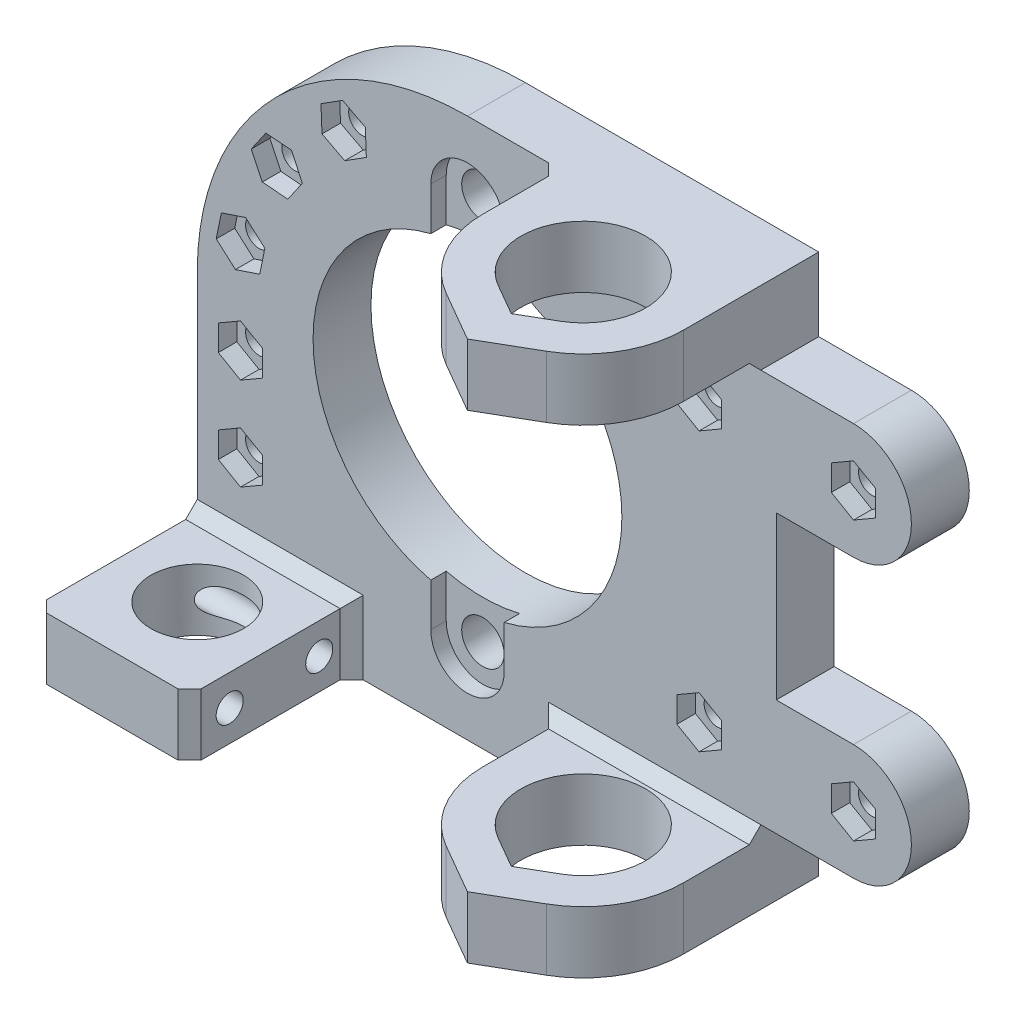
SolidWorks part; units mm, degrees
ref_plane "Front Plane" through (0, 0, 0) normal (0, 0, 1) x (1, 0, 0)
ref_plane "Top Plane" through (0, 0, 0) normal (0, 1, 0) x (1, 0, 0)
ref_plane "Right Plane" through (0, 0, 0) normal (1, 0, 0) x (0, 0, -1)
sketch "Sketch1" plane through (0, 0, 0) normal (0, 1, 0) x (1, 0, 0)
  line L0 (-62.4163, 0) -> (61.9965, 0) construction
  line L1 (-36.5, 35) -> (36.5, 35)
  line L2 (-36.5, 35) -> (-36.5, -35)
  line L3 (-36.5, -35) -> (36.5, -35)
  line L4 (36.5, 35) -> (36.5, -35) construction
  line L5 (-36.5, 35) -> (36.5, -35) construction
  line L6 (-36.5, -35) -> (36.5, 35) construction
  line L7 (36.5, 35) -> (36.5, 25.5)
  line L8 (36.5, 25.5) -> (48.5, 25.5)
  line L9 (48.5, 10.5) -> (38.5, 10.5)
  line L10 (38.5, 10.5) -> (38.5, -10.5)
  line L11 (48.5, -10.5) -> (38.5, -10.5)
  line L12 (36.5, -25.5) -> (48.5, -25.5)
  line L13 (36.5, -35) -> (36.5, -25.5)
  arc A0 (48.5, 25.5) -> (48.5, 10.5) centre (48.5, 18) cw
  arc A1 (48.5, -25.5) -> (48.5, -10.5) centre (48.5, -18) ccw
  point P0 (0, 0)
  point P15 (38.5, 0)
  dimension "D1" = 73
  dimension "D2" = 70
  dimension "D3" = 75
  dimension "D4" = 15
  dimension "D5" = 10
  dimension "D6" = 9.5
extrude "Boss-Extrude1" add sketch "Sketch1" along normal blind 7.5
sketch "Sketch3" plane through (0, 0, 35) normal (0, 0, 1) x (1, 0, 0)
  line L0 (36.5, 7.5) -> (36.5, 0) construction
  line L1 (36.5, 7.5) -> (10.5, 7.5)
  line L2 (36.5, 7.5) -> (36.5, 17.5)
  line L3 (36.5, 17.5) -> (10.5, 17.5) construction
  line L4 (10.5, 7.5) -> (10.5, 17.5)
  line L5 (-36.5, 7.5) -> (36.5, 7.5) construction
  line L6 (-36.5, 0) -> (36.5, 0) construction
  line L7 (23.5, 17.5) -> (23.5, 40.9913) construction
  line L8 (17, 28.7583) -> (23.5, 32.5111)
  line L9 (19.4625, 24.4932) -> (23.5, 26.8242)
  line L10 (17, 28.7583) -> (23.5, 17.5) construction
  line L11 (27.5375, 24.4932) -> (23.5, 26.8242)
  line L12 (30, 28.7583) -> (23.5, 32.5111)
  arc A0 (19.4625, 24.4932) -> (27.5375, 24.4932) centre (23.5, 17.5) ccw
  arc A1 (10.5, 17.5) -> (17, 28.7583) centre (23.5, 17.5) cw
  arc A2 (30, 28.7583) -> (36.5, 17.5) centre (23.5, 17.5) cw
  point P10 (23.5, 17.5)
  dimension "D3" = 16.15
  dimension "D1" = 26
  dimension "D2" = 17.5
  dimension "D4" = 120
extrude "Boss-Extrude3" add sketch "Sketch3" against normal blind 8
mirror "Mirror1" about plane through (0, 0, 0) normal (0, 0, 1) of "Boss-Extrude3"
sketch "Sketch10" plane through (0, 0, 0) normal (0, -1, 0) x (1, 0, 0)
  line L1 (-36.5, 27) -> (-16.5, 27)
  line L2 (-36.5, 27) -> (-36.5, 35)
  line L3 (-36.5, 35) -> (-16.5, 35)
  line L4 (-16.5, 27) -> (-16.5, 35)
  line L6 (-36.5, 35) -> (36.5, 35) construction
  line L7 (31.575, 35) -> (15.425, 35) construction
  point P9 (23.5, 35)
  point P14 (-26.5, 35)
  dimension "D1" = 8
  dimension "D4" = 50
extrude "Boss-Extrude4" add sketch "Sketch10" against normal offset from surface (28.5 mm away) 21 up to face at (22.7812, 7.5, -0.2031) offset beyond the face yes
sketch "Sketch11" plane through (0, 0, 35) normal (0, 0, 1) x (1, 0, 0)
  circle A0 centre (-26.5, 17.5) radius 6
  point P2 (23.5, 17.5)
  dimension "D1" = 12
  dimension "D2" = 50
extrude "Cut-Extrude6" cut sketch "Sketch11" against normal up to next
sketch "Sketch12" plane through (-36.5, 0, 0) normal (-1, 0, 0) x (0, 0, 1)
  line L0 (27, 17.5) -> (35, 17.5) construction
  line L1 (27, 28.5) -> (27, 7.5) construction
  line L2 (35, 28.5) -> (35, 0) construction
  line L3 (27, 23.5) -> (27, 11.5) construction
  circle A0 centre (31, 23.3) radius 1.75
  circle A1 centre (31, 11.7) radius 1.75
  point P12 (31, 21.55)
  point P13 (31, 13.45)
  point P14 (31, 17.5)
  dimension "D2" = 3.5
  dimension "D1" = 8.1
extrude "Cut-Extrude7" cut sketch "Sketch12" against normal up to next
sketch "Sketch6" plane through (0, 0, 0) normal (0, -1, 0) x (1, 0, 0)
  line L0 (-36.5, -35) -> (-36.5, 35) construction
  line L3 (-36.5, 35) -> (36.5, 35) construction
  line L5 (-20.5, 35) -> (-32.5, 35) construction
  line L6 (31.575, 35) -> (15.425, 35) construction
  line L7 (-26.5, 35) -> (23.5, 35) construction
  line L9 (-1.5, 35) -> (-1.5, 0) construction
  circle A0 centre (-1.5, 0) radius 20
  point P3 (-26.5, 35)
  point P5 (-36.5, 0)
  point P10 (23.5, 35)
  point P18 (-1.5, 35)
  dimension "D1" = 40
extrude "Cut-Extrude3" cut sketch "Sketch6" against normal through all
sketch "Sketch15" plane through (0, 0, 0) normal (0, -1, 0) x (1, 0, 0)
  line L0 (-1.5, 35) -> (-1.5, -35) construction
  line L1 (-36.5, 35) -> (36.5, 35) construction
  line L2 (36.5, -35) -> (-36.5, -35) construction
  line L3 (-21.5, 0) -> (18.5, 0) construction
  circle A1 centre (-1.5, 0) radius 20 construction
  circle A2 centre (-1.5, 25) radius 2.75
  circle A3 centre (-1.5, -25) radius 2.75
  point P8 (-1.5, 0)
  dimension "D1" = 5.5
  dimension "D2" = 25
extrude "Cut-Extrude9" cut sketch "Sketch15" against normal through all
sketch "Sketch14" plane through (0, 0, 0) normal (0, -1, 0) x (1, 0, 0)
  line L0 (0, 0) -> (89.7656, 0) construction
  line L1 (38.5, -10.5) -> (38.5, -25.5333) construction
  circle A0 centre (48.5, -18) radius 1.75
  circle A1 centre (28.5, -18) radius 1.75
  circle A2 centre (48.5, 18) radius 1.75
  circle A3 centre (28.5, 18) radius 1.75
  dimension "D1" = 3.5
  dimension "D2" = 20
extrude "Cut-Extrude8" cut sketch "Sketch14" against normal through all
sketch "Sketch19" plane through (0, 7.5, 0) normal (0, 1, 0) x (1, 0, 0)
  line L0 (38.5, 0) -> (82.8981, 0) construction
  line L1 (38.5, -10.5) -> (38.5, 10.5) construction
  line L2 (28.5, -18) -> (48.5, -18) construction
  line L3 (38.5, -18) -> (38.5, 0) construction
  line L4 (25.625, -16.3401) -> (28.5, -14.6802)
  line L5 (48.5, -14.6802) -> (45.625, -16.3401)
  line L6 (45.625, -16.3401) -> (45.625, -19.6599)
  line L7 (45.625, -19.6599) -> (48.5, -21.3198)
  line L8 (48.5, -21.3198) -> (51.375, -19.6599)
  line L9 (51.375, -19.6599) -> (51.375, -16.3401)
  line L10 (51.375, -16.3401) -> (48.5, -14.6802)
  line L11 (25.625, -19.6599) -> (25.625, -16.3401)
  line L12 (28.5, -21.3198) -> (25.625, -19.6599)
  line L13 (31.375, -19.6599) -> (28.5, -21.3198)
  line L14 (31.375, -16.3401) -> (31.375, -19.6599)
  line L15 (28.5, -14.6802) -> (31.375, -16.3401)
  line L16 (48.5, 21.3198) -> (51.375, 19.6599)
  line L17 (45.625, 19.6599) -> (48.5, 21.3198)
  line L18 (51.375, 16.3401) -> (48.5, 14.6802)
  line L19 (51.375, 19.6599) -> (51.375, 16.3401)
  line L20 (45.625, 16.3401) -> (45.625, 19.6599)
  line L21 (48.5, 14.6802) -> (45.625, 16.3401)
  line L22 (28.5, 14.6802) -> (31.375, 16.3401)
  line L23 (31.375, 16.3401) -> (31.375, 19.6599)
  line L24 (31.375, 19.6599) -> (28.5, 21.3198)
  line L25 (28.5, 21.3198) -> (25.625, 19.6599)
  line L26 (25.625, 19.6599) -> (25.625, 16.3401)
  line L27 (25.625, 16.3401) -> (28.5, 14.6802)
  circle A0 centre (48.5, -18) radius 2.875 construction
  circle A1 centre (48.5, 18) radius 2.875 construction
  dimension "D1" = 5.75
extrude "Cut-Extrude13" cut sketch "Sketch19" against normal blind 2.4
fillet "Fillet2" radius 35 1 edges at (-36.5, 3.75, -35)
chamfer "Chamfer2" distance 1.5 angle 45 8 edges at (-16.5, 28.5, 31) (-36.5, 28.5, 31) (-26.5, 7.5, 27) (-16.5, 7.5, 31) (23.5, 7.5, -27) (10.5, 7.5, -31)
sketch "Sketch17" plane through (0, 0, 0) normal (0, -1, 0) x (1, 0, 0)
  line L0 (-1.5, 0) -> (-36.5, 0) construction
  line L1 (-1.5, 0) -> (-16.5, -25.9808) construction
  line L2 (-1.5, 0) -> (-27.4808, 15) construction
  line L3 (-26.1909, 17.04) -> (-30.8939, 6) construction
  line L4 (-30.8939, 6) -> (-30.8939, -6) construction
  line L5 (-30.8939, -6) -> (-26.1909, -17.04) construction
  line L6 (-26.1909, -17.04) -> (-17.5373, -25.3536) construction
  line L7 (-30.8939, 6) -> (-30.8939, 18) construction
  circle A0 centre (-1.5, 0) radius 30 construction
  circle A1 centre (-30.8939, 6) radius 1.75
  circle A2 centre (-30.8939, -6) radius 1.75
  circle A3 centre (-30.8939, 18) radius 1.75
  circle A4 centre (-26.1909, -17.04) radius 1.75
  circle A5 centre (-17.5373, -25.3536) radius 1.75
  point P0 (-1.5, 0)
  point P5 (-31.5, 0)
  dimension "D2" = 60
  dimension "D5" = 3.5
  dimension "D1" = 30
  dimension "D3" = 5
  dimension "D4" = 12
extrude "Cut-Extrude11" cut sketch "Sketch17" against normal up to next
sketch "Sketch18" plane through (0, 7.5, 0) normal (0, 1, 0) x (1, 0, 0)
  line L0 (-30.8939, -18) -> (-1.5, 0) construction
  line L1 (-28.0189, -19.6599) -> (-28.0189, -16.3401)
  line L2 (-28.0189, -16.3401) -> (-30.8939, -14.6802)
  line L3 (-30.8939, -14.6802) -> (-33.7689, -16.3401)
  line L4 (-33.7689, -16.3401) -> (-33.7689, -19.6599)
  line L5 (-33.7689, -19.6599) -> (-30.8939, -21.3198)
  line L6 (-30.8939, -21.3198) -> (-28.0189, -19.6599)
  line L7 (-28.0189, -4.3401) -> (-30.8939, -2.6802)
  line L8 (-30.8939, -2.6802) -> (-33.7689, -4.3401)
  line L9 (-33.7689, -4.3401) -> (-33.7689, -7.6599)
  line L10 (-33.7689, -7.6599) -> (-30.8939, -9.3198)
  line L11 (-30.8939, -9.3198) -> (-28.0189, -7.6599)
  line L12 (-28.0189, -7.6599) -> (-28.0189, -4.3401)
  line L13 (-27.745, 7.0513) -> (-30.2299, 9.2527)
  line L14 (-30.2299, 9.2527) -> (-33.3788, 8.2013)
  line L15 (-33.3788, 8.2013) -> (-34.0428, 4.9487)
  line L16 (-34.0428, 4.9487) -> (-31.5578, 2.7473)
  line L17 (-31.5578, 2.7473) -> (-28.4089, 3.7987)
  line L18 (-28.4089, 3.7987) -> (-27.745, 7.0513)
  line L19 (-22.8818, 16.7731) -> (-24.3052, 19.7723)
  line L20 (-24.3052, 19.7723) -> (-27.6143, 20.0391)
  line L21 (-27.6143, 20.0391) -> (-29.4999, 17.3069)
  line L22 (-29.4999, 17.3069) -> (-28.0765, 14.3077)
  line L23 (-28.0765, 14.3077) -> (-24.7675, 14.0409)
  line L24 (-24.7675, 14.0409) -> (-22.8818, 16.7731)
  line L25 (-14.5976, 23.8112) -> (-14.7317, 27.1283)
  line L26 (-14.7317, 27.1283) -> (-17.6714, 28.6707)
  line L27 (-17.6714, 28.6707) -> (-20.477, 26.896)
  line L28 (-20.477, 26.896) -> (-20.3429, 23.5789)
  line L29 (-20.3429, 23.5789) -> (-17.4032, 22.0365)
  line L30 (-17.4032, 22.0365) -> (-14.5976, 23.8112)
  line L31 (-1.5, 0) -> (-30.8939, -6) construction
  line L32 (-1.5, 0) -> (-30.8939, 6) construction
  line L33 (-1.5, 0) -> (-26.1909, 17.04) construction
  line L34 (-1.5, 0) -> (-17.5373, 25.3536) construction
  line L35 (-36.5, 0) -> (-36.5, -35) construction
  circle A0 centre (-30.8939, -18) radius 2.875 construction
  circle A1 centre (-30.8939, -6) radius 2.875 construction
  circle A2 centre (-30.8939, 6) radius 2.875 construction
  circle A3 centre (-26.1909, 17.04) radius 2.875 construction
  circle A4 centre (-17.5373, 25.3536) radius 2.875 construction
  point P0 (-30.8939, -18)
  point P1 (-30.8939, -6)
  point P3 (-30.8939, 6)
  point P5 (-26.1909, 17.04)
  point P7 (-17.5373, 25.3536)
  point P43 (-1.5, 0)
  point P55 (-30.8939, -18)
  dimension "D1" = 5.75
extrude "Cut-Extrude12" cut sketch "Sketch18" against normal blind 2.4
sketch "Sketch20" plane through (0, 7.5, 0) normal (0, 1, 0) x (1, 0, 0)
  line L0 (-1.5, 25) -> (-1.5, -25) construction
  line L1 (3.25, 25) -> (3.25, -25)
  line L2 (-6.25, 25) -> (-6.25, -25)
  arc A0 (3.25, 25) -> (-6.25, 25) centre (-1.5, 25) ccw
  arc A1 (-6.25, -25) -> (3.25, -25) centre (-1.5, -25) ccw
  circle A2 centre (-1.5, 25) radius 2.75 construction
  circle A3 centre (-1.5, -25) radius 2.75 construction
  point P2 (-1.5, 0)
  dimension "D1" = 9.5
extrude "Cut-Extrude14" cut sketch "Sketch20" against normal blind 2
move or copy body "Body-Move/Copy1" bodies to move or copy 122 copy no rotation origin (0, 15.25, 0) rotation axis (1, 0, 0) rotation angle 90
